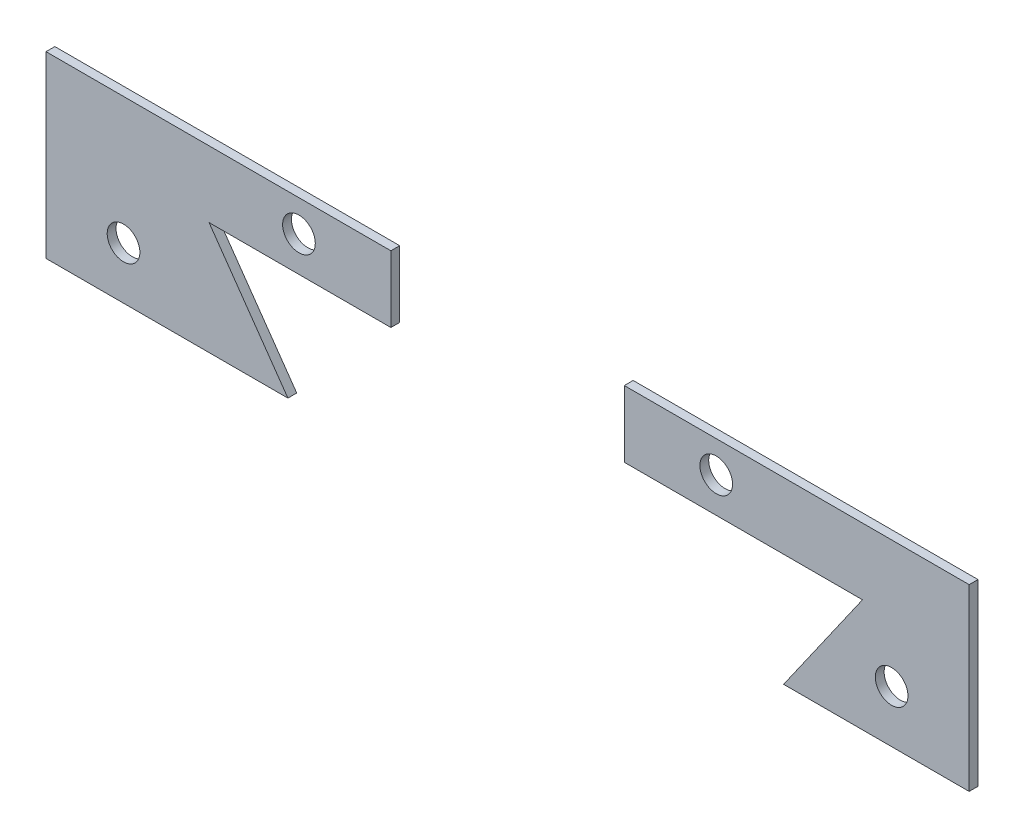
SolidWorks part; units mm, degrees
material "Plain Carbon Steel"
ref_plane "Front Plane" through (0, 0, 0) normal (0, 0, 1) x (1, 0, 0)
ref_plane "Top Plane" through (0, 0, 0) normal (0, 1, 0) x (1, 0, 0)
ref_plane "Right Plane" through (0, 0, 0) normal (1, 0, 0) x (0, 0, -1)
sketch "Sketch4" plane through (0, 0, 0) normal (0, 0, 1) x (1, 0, 0)
  point P0 (0, 0)
  line B0 (-63.5, -15.875) -> (63.5, -15.875)
  line B1 (63.5, -15.875) -> (63.5, 0)
  line B2 (63.5, 0) -> (36.5092, 0)
  line B3 (36.5092, 0) -> (47.625, 15.875)
  line B4 (47.625, 15.875) -> (16.0563, 15.875)
  line B5 (-39.8731, 15.875) -> (-28.7573, 0)
  line B6 (-28.7573, 0) -> (-63.5, 0)
  line B7 (-36.5092, 0) -> (-47.625, 15.875)
  line B8 (-16.0563, -3.175) -> (16.0563, -3.175)
  line B9 (16.0563, -3.175) -> (16.0563, 15.875)
  line B10 (-16.0563, 15.875) -> (-39.8731, 15.875)
  line B11 (-63.5, 0) -> (-63.5, 31.75)
  line B12 (-63.5, 31.75) -> (63.5, 31.75)
  line B13 (63.5, 31.75) -> (63.5, 0)
  line B14 (-16.0563, 15.875) -> (16.0563, 15.875)
  line B15 (-36.5092, 0) -> (36.5092, 0) construction
  line B16 (-28.702, 21.082) -> (28.702, 21.082) construction
  line B17 (-52.832, 7.9375) -> (52.832, 7.9375) construction
  circle B18 centre (0, 6.35) radius 18.669 construction
sketch_block_instance "dovetail pair-1"
sketch_block "dovetail pair" parameters "D8"=37.338, "D1"=55, "D2"=127, "D3"=6.35, "D4"=15.875, "D5"=31.75, "D6"=95.25, "D7"=19.05, "D9"=55, "D10"=31.75, "D11"=50.8, "D12"=23.876, "D13"=7.874, "D14"=10.668, "D15"=34.798, "D16"=21.082, "D17"=7.9375
sketch "Sketch1" plane through (0, 0, 0) normal (0, 0, 1) x (1, 0, 0)
  line L0 (-63.5, 31.75) -> (63.5, 31.75) construction
  line L1 (-63.5, 0) -> (-63.5, 31.75) construction
  line L2 (-28.7573, 0) -> (-63.5, 0) construction
  line L3 (-39.8731, 15.875) -> (-28.7573, 0) construction
  line L4 (-16.0563, 15.875) -> (-39.8731, 15.875) construction
  line L5 (-16.0563, 15.875) -> (16.0563, 15.875) construction
  line L6 (47.625, 15.875) -> (16.0563, 15.875) construction
  line L7 (36.5092, 0) -> (47.625, 15.875) construction
  line L8 (63.5, 0) -> (36.5092, 0) construction
  line L9 (63.5, 31.75) -> (63.5, 0) construction
  line L10 (-63.5, 31.75) -> (63.5, 31.75) construction
  line L11 (-63.5, 0) -> (-63.5, 31.75) construction
  line L12 (-63.5, 0.762) -> (-30.2211, 0.762)
  line L13 (-30.2211, 0.762) -> (-41.0701, 16.256)
  line L14 (16.0563, 15.875) -> (16.0563, 16.256) construction
  line L15 (-41.0701, 16.256) -> (-16.0563, 16.256)
  line L16 (-16.0563, 16.256) -> (-16.0563, 25.4)
  line L17 (-16.0563, 25.4) -> (-63.5, 25.4)
  line L18 (-28.7573, 0) -> (-63.5, 0) construction
  line L19 (-63.5, 25.4) -> (-63.5, 0.762)
  line L21 (-39.8731, 15.875) -> (-28.7573, 0) construction
  line L24 (-16.0563, 15.875) -> (-16.0563, 16.256) construction
  line L25 (16.0563, 16.256) -> (48.822, 16.256)
  line L26 (48.822, 16.256) -> (37.973, 0.762)
  line L27 (37.973, 0.762) -> (63.5, 0.762)
  line L28 (63.5, 0.762) -> (63.5, 25.4)
  line L30 (63.5, 25.4) -> (16.0563, 25.4)
  line L33 (-16.0563, 15.875) -> (-39.8731, 15.875) construction
  line L34 (-16.0563, 15.875) -> (16.0563, 15.875) construction
  line L35 (47.625, 15.875) -> (16.0563, 15.875) construction
  line L36 (36.5092, 0) -> (47.625, 15.875) construction
  line L37 (63.5, 0) -> (36.5092, 0) construction
  line L38 (63.5, 31.75) -> (63.5, 0) construction
  line L39 (16.0563, 25.4) -> (16.0563, 16.256)
  dimension "D1" = 25.4
  dimension "D2" = 0.762
  dimension "D3" = 0.762
  dimension "D4" = 0.762
  dimension "D5" = 0.762
extrude "Boss-Extrude1" add sketch "Sketch1" along normal blind 1.2141
hole_wizard "#8 Clearance Hole1" positions "Sketch2" profile "Sketch3" hole size "#8" standard "ANSI Inch" end condition through all
sketch "Sketch2" plane through (0, -15.875, 1.2141) normal (0, 0, 1) x (1, 0, 0)
  point P32 (-28.702, 36.957)
  point P34 (-52.832, 23.8125)
  point P36 (28.702, 36.957)
  point P38 (52.832, 23.8125)
sketch "Sketch3" plane through (-28.702, 21.082, 1.2141) normal (1, 0, 0) x (0, -1, 0)
  line L0 (0, 0) -> (0, 1.2141)
  line L1 (0, 1.2141) -> (2.2479, 1.2141)
  line L2 (2.2479, 1.2141) -> (2.2479, 0)
  line L3 (2.2479, 0) -> (0, 0)
  line L4 (0, -6.35) -> (0, 107.95) construction
  dimension "Thru Hole Dia." = 4.4958
  dimension "Thru Hole Depth" = 1.2141
equation "\"dovetail-angle\" = 55"
equation "\"dovetail-stock-width\" = 5"
equation "\"dovetail-stock-height\" = 1.25"
equation "\"dovetail-depth\" = 0.5 * \"dovetail-stock-height\""
equation "\"dovetail-throat-width\" = \"dovetail-stock-width\" - (2 * \"dovetail-depth\")"
equation "\"delta-x\" = 6"
equation "\"delta-y\" = 3"
equation "\"gib-thickness\" = 0.25"
equation "\"x-slide-length\" = \"dovetail-stock-width\" + \"delta-x\""
equation "\"y-slide-length\" = \"dovetail-stock-width\" + \"delta-y\""
equation "\"dog-point-diam\" = .149"
equation "\"dog-point-length\" = .067"
equation "\"dovetail-double-height\" = 2 * \"dovetail-depth\" + 0.5"
equation "\"acme-major-diam\" = .5"
equation "\"acme-pitch-diam\" = 0.45"
equation "\"acme-minor-diam\" = 0.4"
equation "\"acme-nut-od\" = 1.47"
equation "\"acme-nut-length\" = 1"
equation "\"acme-nut-trim-height\" = .75"
equation "\"screw-bearing-od\" = 0.5"
equation "\"screw-bearing-length\" = .375"
equation "\"screw-bearing-id\" = .375"
equation "\"end-plate-thickness\" = \"screw-bearing-length\""
equation "\"screw-add-length\" = 2 * \"end-plate-thickness\" + 1 + 0.5"
equation "\"x-screw-length\" = \"x-slide-length\" + \"screw-add-length\""
equation "\"y-screw-length\" = \"y-slide-length\" + \"screw-add-length\""
equation "\"acme-nut-mount-hole-space-horz\" = 0.95"
equation "\"acme-nut-mount-hole-space-vert\" = 0.5 * \"acme-nut-length\""
equation "\"vise-hole-center-dist\" = 6.75"
equation "\"wiper_plate_clearance\" = .03"
equation "\"D2@Sketch1\"=\"wiper_plate_clearance\""
equation "\"D3@Sketch1\"=\"wiper_plate_clearance\""
equation "\"D4@Sketch1\"=\"wiper_plate_clearance\""
equation "\"D5@Sketch1\"=\"wiper_plate_clearance\""
equation "\"D2@dovetail pair\"=\"dovetail-stock-width\""
equation "\"D1@dovetail pair\"=\"dovetail-angle\""
equation "\"D3@dovetail pair\"=\"gib-thickness\""
equation "\"D4@dovetail pair\"=\"dovetail-depth\""
equation "\"D5@dovetail pair\"=\"dovetail-stock-height\""
equation "\"D6@dovetail pair\"=\"dovetail-throat-width\""
equation "\"D10@dovetail pair\"=\"dovetail-stock-height\""
equation "\"D7@dovetail pair\"=\"acme-nut-trim-height\""
equation "\"D8@dovetail pair\"=\"acme-nut-od\""
equation "\"D9@dovetail pair\"=\"dovetail-angle\""
equation "\"D17@dovetail pair\"=\"dovetail-depth\"/2"
